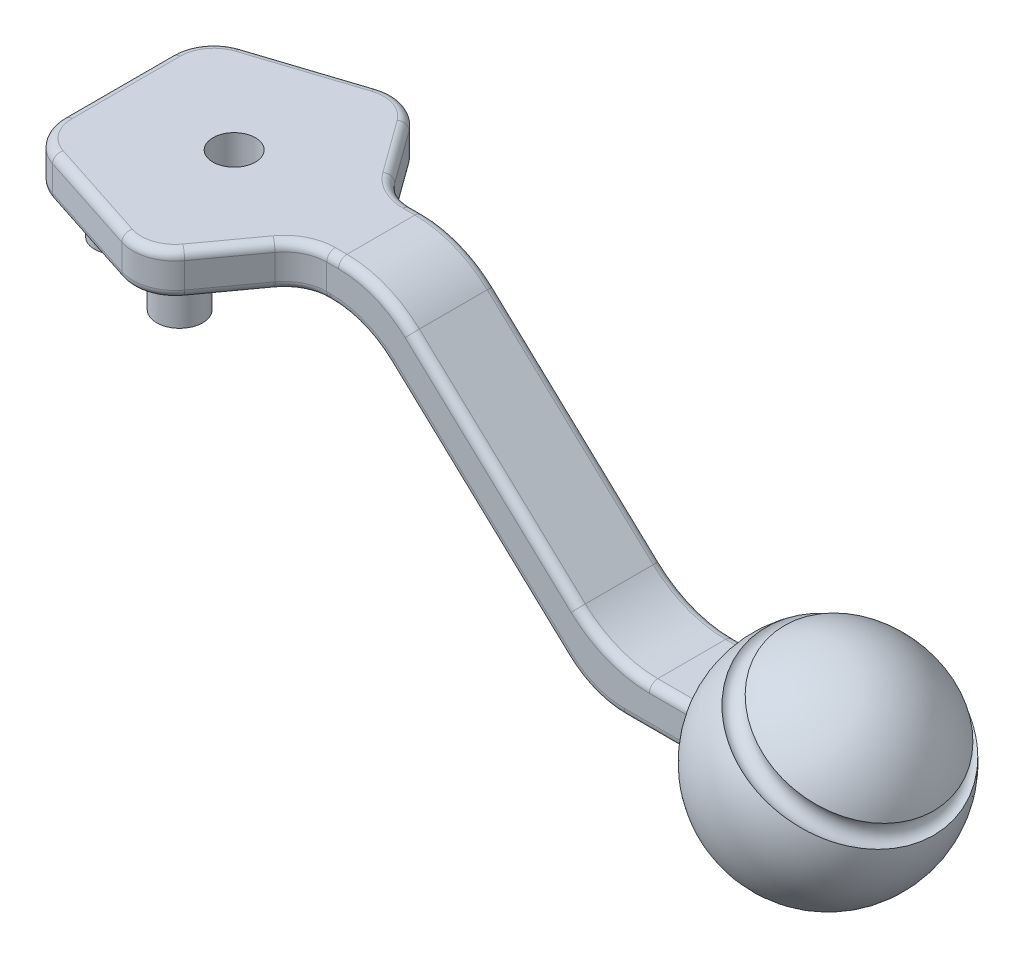
SolidWorks part; units mm, degrees
ref_plane "Front Plane" through (0, 0, 0) normal (0, 0, 1) x (1, 0, 0)
ref_plane "Top Plane" through (0, 0, 0) normal (0, 1, 0) x (1, 0, 0)
ref_plane "Right Plane" through (0, 0, 0) normal (1, 0, 0) x (0, 0, -1)
sketch "Sketch1" plane through (0, 0, 0) normal (0, 1, 0) x (1, 0, 0)
  line L0 (0, 31.75) -> (0, -31.75)
  circle A1 centre (0, 0) radius 31.75
  dimension "D1" = 63.5
revolve "Revolve1" add sketch "Sketch1" angle 360 about L0 region at (13.4751, 0, 0)
sketch "Sketch4" plane through (0, 0, 0) normal (0, 0, 1) x (1, 0, 0)
  line L0 (0, 0) -> (-31.75, 0) construction
  line L1 (-31.1085, 6.35) -> (-53.34, 6.35)
  line L2 (-53.34, 6.35) -> (-121.3358, 69.85)
  line L3 (-121.3358, 69.85) -> (-177.8, 69.85)
  line L4 (-31.1085, -6.35) -> (-58.348, -6.35)
  line L5 (-58.348, -6.35) -> (-126.3438, 57.15)
  line L6 (-126.3438, 57.15) -> (-177.8, 57.15)
  line L7 (-177.8, 69.85) -> (-177.8, 57.15)
  line L8 (-31.1085, 6.35) -> (0, 6.35)
  line L9 (0, 6.35) -> (0, 0)
  line L10 (0, 0) -> (0, -6.35)
  line L11 (0, -6.35) -> (-31.1085, -6.35)
  circle A0 centre (0, 0) radius 31.75 construction
  dimension "D1" = 6.35
  dimension "D2" = 53.34
  dimension "D3" = 121.3358
  dimension "D4" = 177.8
  dimension "D5" = 63.5
  dimension "D6" = 12.7
extrude "Boss-Extrude1" add sketch "Sketch4" along normal mid plane 25.4 separate body contours L1 L2 L3 L7 L6 L5 L4 | L11 L4 L5 L6 L7 L3 L2 L1 L8 L9 L10 region at (-89.0163, 31.4551, 0)
combine bodies "Combine2" operation type add bodies to combine 101 103
fillet "Fillet5" radius 31.75 2 edges at (-53.34, 6.35, 0) (-121.3358, 69.85, 0)
fillet "Fillet6" radius 25.4 2 edges at (-58.348, -6.35, 0) (-126.3438, 57.15, 0)
sketch "Sketch5" plane through (0, 69.85, 0) normal (0, 1, 0) x (1, 0, 0)
  line L0 (-177.8, -12.7) -> (-177.8, 12.7) construction
  line L1 (-134.6303, 0) -> (-164.4598, 41.0568)
  line L2 (-164.4598, 41.0568) -> (-212.725, 25.3745)
  line L3 (-212.725, 25.3745) -> (-212.725, -25.3745)
  line L4 (-212.725, -25.3745) -> (-164.4598, -41.0568)
  line L5 (-164.4598, -41.0568) -> (-134.6303, 0)
  line L6 (-121.3358, 0) -> (-177.8, 0) construction
  line L7 (-121.3358, -12.7) -> (-121.3358, 12.7) construction
  line L8 (-164.4598, -41.0568) -> (-169.951, -24.1568) construction
  line L9 (-212.725, -25.3745) -> (-198.349, -14.9297)
  line L10 (-212.725, 25.3745) -> (-198.349, 14.9297) construction
  line L11 (-164.4598, 41.0568) -> (-169.951, 24.1568) construction
  line L12 (-133.8559, 12.7) -> (-177.8, 12.7)
  line L13 (-177.8, 12.7) -> (-177.8, -12.7)
  line L14 (-177.8, -12.7) -> (-133.8559, -12.7)
  line L15 (-133.8559, -12.7) -> (-133.8559, 12.7)
  line L16 (-133.8559, 12.7) -> (-177.8, 12.7)
  line L17 (-177.8, 12.7) -> (-177.8, -12.7)
  line L18 (-177.8, -12.7) -> (-133.8559, -12.7)
  line L20 (-133.8559, -12.7) -> (-133.8559, 12.7)
  circle A0 centre (-177.8, 0) radius 34.925 construction
  circle A1 centre (-177.8, 0) radius 6.35
  circle A2 centre (-177.8, 0) radius 25.4 construction
  circle A3 centre (-169.951, 24.1568) radius 6.35
  circle A4 centre (-198.349, 14.9297) radius 6.35
  circle A5 centre (-198.349, -14.9297) radius 6.35
  circle A6 centre (-169.951, -24.1568) radius 6.8754
  line M11 (-133.8559, 12.7) -> (-177.8, 12.7)
  line M12 (-177.8, 12.7) -> (-177.8, -12.7)
  line M13 (-177.8, -12.7) -> (-133.8559, -12.7)
  dimension "D1" = 69.85
  dimension "D3" = 12.7
  dimension "D4" = 50.8
  dimension "D5" = 12.7
  dimension "D6" = 12.7
  dimension "D7" = 12.7
  dimension "D8" = 13.7508
  dimension "D2" = 0
extrude "Boss-Extrude2" add sketch "Sketch5" against normal up to surface (12.7 mm away) contours A1 L1 L2 L3 L4 L5 M12 M11 M13 | A1 L5 L1 M12 M13 M11 | L17 A1 | A4 | A3 | A6 | A5 region at (-157.2769, 69.85, 0) region at (-160.8287, 69.85, -13.7717) region at (-180.495, 69.85, 0) up to face at (-157.0799, 57.15, 0)
extrude "Cut-Extrude1" cut sketch "Sketch5<3>" against normal through all contours L17 A1 | L17 A1 region at (-175.105, 69.85, 0) region at (-180.495, 69.85, 0)
sketch "Sketch5<3>" plane through (0, 69.85, 0) normal (0, 1, 0) x (1, 0, 0) same geometry as "Sketch5"
extrude "Boss-Extrude3" add sketch "Sketch5<4>" against normal blind 12.7 from surface contours A4 | A3 | A5 | A6 region at (-200.2558, 69.85, 9.0614) region at (-169.951, 69.85, -24.1568) region at (-198.349, 69.85, -14.9297) region at (-169.951, 69.85, 24.1568) starting at face at (-171.45, 57.15, 0)
sketch "Sketch5<4>" plane through (0, 69.85, 0) normal (0, 1, 0) x (1, 0, 0) same geometry as "Sketch5"
fillet "Fillet7" radius 12.7 6 edges at (-143.8574, 63.5, -12.7) (-164.4598, 63.5, -41.0568) (-212.725, 63.5, -25.3745) (-212.725, 63.5, 25.3745) (-164.4598, 63.5, 41.0568) (-143.8574, 63.5, 12.7)
fillet "Fillet2" radius 2.54 42 edges at (-136.8732, 57.15, -12.7) (-135.6211, 69.85, -12.7) (-38.365, -6.35, 12.7) (-92.3459, 25.4, 12.7) (-136.8732, 57.15, 12.7) (-135.6211, 69.85, 12.7) (-87.3379, 38.1, 12.7) (-34.609, 6.35, 12.7) (-38.365, -6.35, -12.7) (-92.3459, 25.4, -12.7) (-34.609, 6.35, -12.7) (-87.3379, 38.1, -12.7) (-57.6497, -4.5792, 12.7) (-127.0421, 55.3792, 12.7) (-57.6497, -4.5792, -12.7) (-127.0421, 55.3792, -12.7) (-52.4671, 8.5635, 12.7) (-122.2087, 67.6365, 12.7) (-52.4671, 8.5635, -12.7) (-122.2087, 67.6365, -12.7) (-143.1521, 57.15, -14.0842) (-153.3486, 57.15, -25.7635) (-165.3863, 57.15, -38.2055) (-188.5924, 57.15, -33.2156) (-210.2995, 57.15, -23.6123) (-212.725, 57.15, 0) (-210.2995, 57.15, 23.6123) (-188.5924, 57.15, 33.2156) (-165.3863, 57.15, 38.2055) (-153.3486, 57.15, 25.7635) (-143.1521, 57.15, 14.0842) (-143.1521, 69.85, -14.0842) (-153.3486, 69.85, -25.7635) (-165.3863, 69.85, -38.2055) (-188.5924, 69.85, -33.2156) (-210.2995, 69.85, -23.6123) (-212.725, 69.85, 0) (-210.2995, 69.85, 23.6123) (-188.5924, 69.85, 33.2156) (-165.3863, 69.85, 38.2055) (-153.3486, 69.85, 25.7635) (-143.1521, 69.85, 14.0842)
sketch "Sketch7" plane through (0, 0, 0) normal (0, 0, 1) x (1, 0, 0)
  line L0 (0, 0) -> (26.2571, 45.4786) construction
  line L1 (0, 0) -> (0, 66.9347) construction
  line L2 (0, 0) -> (-42.7533, 74.0508) construction
  arc A0 (-31.1085, -6.35) -> (-31.1085, 6.35) centre (0, 0) ccw construction
  arc A1 (-31.1085, -6.35) -> (-31.1085, 6.35) centre (0, 0) ccw
  circle A2 centre (-15.875, 27.4963) radius 3.175
  dimension "D3" = 6.35
  dimension "D1" = 30
  dimension "D2" = 30
revolve "Cut-Revolve1" cut sketch "Sketch7" angle 360 about L0 region at (-15.1871, 26.3049, 0) region at (-16.5343, 28.6382, 0)
sketch "Sketch8" plane through (0, 69.85, 0) normal (0, 1, 0) x (1, 0, 0)
  circle A0 centre (-177.8, 0) radius 6.35 construction
  circle A1 centre (-177.8, 0) radius 6.35
  point P5 (0, 0)
